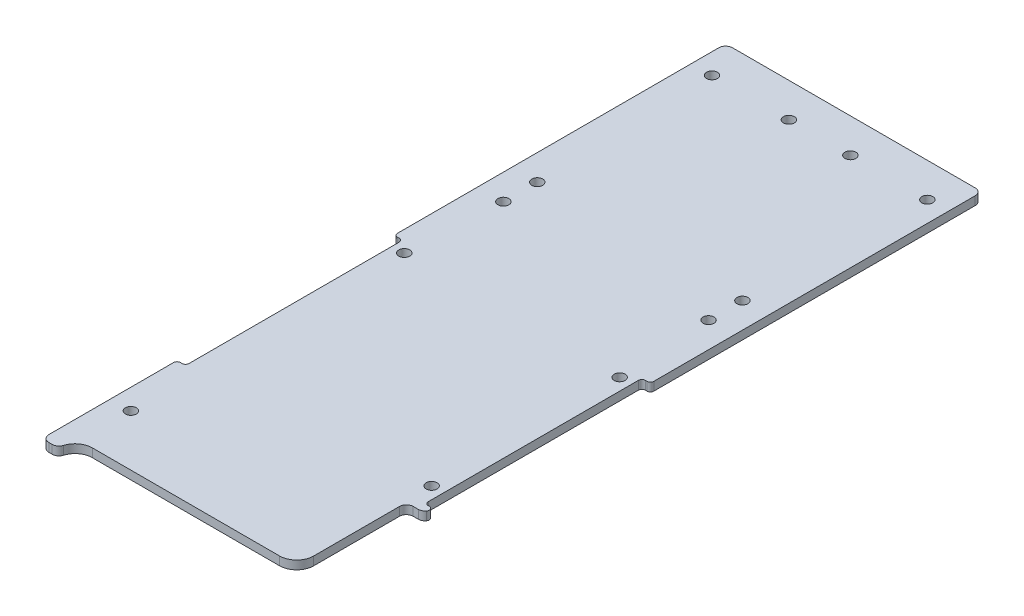
SolidWorks part; units mm, degrees
ref_plane "Front Plane" through (0, 0, 0) normal (0, 0, 1) x (1, 0, 0)
ref_plane "Top Plane" through (0, 0, 0) normal (0, 1, 0) x (1, 0, 0)
ref_plane "Right Plane" through (0, 0, 0) normal (1, 0, 0) x (0, 0, -1)
sketch "Sketch1" plane through (0, 0, 0) normal (0, 1, 0) x (1, 0, 0)
  line L0 (-39.9997, 0) -> (-39.9997, 114.3) construction
  line L1 (-47.625, 127) -> (47.625, 127)
  line L2 (-47.625, 127) -> (-47.625, -127)
  line L3 (-47.625, -127) -> (47.625, -127)
  line L4 (47.625, 127) -> (47.625, -127)
  line L5 (-47.625, 127) -> (47.625, -127) construction
  line L6 (-47.625, -127) -> (47.625, 127) construction
  line L7 (0, 0) -> (0, 127) construction
  line L8 (-39.9997, 0) -> (-39.9997, -101.6) construction
  line L9 (-39.9997, 0) -> (0, 0) construction
  line L10 (-41.275, -127) -> (-41.275, -120.65)
  line L11 (-41.275, -120.65) -> (41.275, -120.65)
  line L12 (41.275, -120.65) -> (41.275, -127)
  line L13 (-39.9997, 114.3) -> (-11.4247, 114.3) construction
  line L14 (39.9997, 114.3) -> (11.4247, 114.3) construction
  circle A0 centre (-39.9997, 114.3) radius 2.032
  circle A1 centre (-39.9997, 0) radius 2.032
  circle A2 centre (-39.9997, -101.6) radius 2.032
  circle A3 centre (39.9997, -101.6) radius 2.032
  circle A4 centre (39.9997, 0) radius 2.032
  circle A5 centre (39.9997, 114.3) radius 2.032
  circle A6 centre (-11.4247, 114.3) radius 2.032
  circle A7 centre (11.4247, 114.3) radius 2.032
  circle A8 centre (-39.9997, -69.85) radius 2.032
  circle A9 centre (39.9997, -69.85) radius 2.032
  point P0 (0, 0)
  dimension "D4" = 4.064
  dimension "D10" = 28.575
  dimension "D1" = 95.25
  dimension "D2" = 254
  dimension "D3" = 7.6253
  dimension "D5" = 12.7
  dimension "D6" = 25.4
  dimension "D7" = 6.35
  dimension "D8" = 6.35
  dimension "D9" = 6.35
  dimension "D11" = 69.85
extrude "Boss-Extrude1" add sketch "Sketch1" along normal blind 3.175 contours L4 L1 L2 L3 A4 A0 A1 A2 A3 A5 | A8 | A3 region at (0, 0, -2.6944) region at (39.9997, 0, 101.6) region at (-39.9997, 0, 69.85)
fillet "Fillet1" radius 2.54 4 edges at (-47.625, 1.5875, -127) (47.625, 1.5875, -127) (47.625, 1.5875, 127) (-47.625, 1.5875, 127)
fillet "Fillet2" radius 2.54 2 edges at (41.275, 1.5875, 127) (-41.275, 1.5875, 127)
fillet "Fillet3" radius 6.35 2 edges at (41.275, 1.5875, 120.65) (-41.275, 1.5875, 120.65)
sketch "Sketch2" plane through (0, 0, 0) normal (0, -1, 0) x (1, 0, 0)
  line L1 (43.815, 127) -> (45.085, 127) construction
  line L2 (40.6451, 123.5787) -> (40.6451, 79.8881)
  line L3 (40.6451, 79.8881) -> (47.625, 79.8881)
  line L11 (47.625, -124.46) -> (47.625, 124.46) construction
  line L12 (43.815, 127) -> (45.085, 127)
  line L13 (47.625, 79.8881) -> (47.625, 124.46)
  arc A0 (35.2956, 120.65) -> (41.3809, 125.1857) centre (35.2956, 127) ccw construction
  arc A1 (43.815, 127) -> (41.3809, 125.1857) centre (43.815, 124.46) ccw construction
  arc A2 (47.625, 124.46) -> (45.085, 127) centre (45.085, 124.46) ccw construction
  arc A3 (40.6451, 123.5787) -> (41.3809, 125.1857) centre (35.2956, 127) ccw
  arc A4 (43.815, 127) -> (41.3809, 125.1857) centre (43.815, 124.46) ccw
  arc A5 (47.625, 124.46) -> (45.085, 127) centre (45.085, 124.46) ccw
  dimension "D2" = 47.1119
  dimension "D1" = 6.9799
extrude "Cut-Extrude1" cut sketch "Sketch2" against normal through all
fillet "Fillet4" radius 6.35 1 edges at (40.6451, 1.5875, 123.5787)
fillet "Fillet5" radius 2.54 2 edges at (47.625, 1.5875, 79.8881) (40.6451, 1.5875, 79.8881)
sketch "Sketch3" plane through (0, 0, 0) normal (0, -1, 0) x (1, 0, 0)
  line L0 (-36.3024, -49.7791) -> (-39.9092, -49.7791) construction
  line L1 (-40.4172, -49.276) -> (-40.4172, -45.7043) construction
  line L2 (-35.7944, -45.7043) -> (-35.7944, -49.276) construction
  line L3 (-39.9092, -45.2013) -> (-36.3024, -45.2013) construction
  line L4 (-36.3024, -37.2027) -> (-39.9092, -37.2027) construction
  line L5 (-35.7944, -33.1279) -> (-35.7944, -36.6996) construction
  line L6 (-40.4172, -36.6996) -> (-40.4172, -33.1279) construction
  line L7 (-39.9092, -32.6249) -> (-36.3024, -32.6249) construction
  line L8 (36.2908, -32.6249) -> (39.8976, -32.6249) construction
  line L9 (40.4056, -33.1279) -> (40.4056, -36.6996) construction
  line L10 (39.8976, -37.2027) -> (36.2908, -37.2027) construction
  line L11 (35.7828, -36.6996) -> (35.7828, -33.1279) construction
  line L12 (36.2908, -45.2013) -> (39.8976, -45.2013) construction
  line L13 (35.7828, -49.276) -> (35.7828, -45.7043) construction
  line L14 (40.4056, -45.7043) -> (40.4056, -49.276) construction
  line L15 (39.8976, -49.7791) -> (36.2908, -49.7791) construction
  line L16 (-36.3024, -49.7791) -> (-39.9092, -49.7791)
  line L17 (-40.4172, -49.276) -> (-40.4172, -45.7043)
  line L18 (-35.7944, -45.7043) -> (-35.7944, -49.276)
  line L19 (-39.9092, -45.2013) -> (-36.3024, -45.2013)
  line L20 (-36.3024, -37.2027) -> (-39.9092, -37.2027)
  line L21 (-35.7944, -33.1279) -> (-35.7944, -36.6996)
  line L22 (-40.4172, -36.6996) -> (-40.4172, -33.1279)
  line L23 (-39.9092, -32.6249) -> (-36.3024, -32.6249)
  line L24 (36.2908, -32.6249) -> (39.8976, -32.6249)
  line L25 (40.4056, -33.1279) -> (40.4056, -36.6996)
  line L26 (39.8976, -37.2027) -> (36.2908, -37.2027)
  line L27 (35.7828, -36.6996) -> (35.7828, -33.1279)
  line L28 (36.2908, -45.2013) -> (39.8976, -45.2013)
  line L29 (35.7828, -49.276) -> (35.7828, -45.7043)
  line L30 (40.4056, -45.7043) -> (40.4056, -49.276)
  line L31 (39.8976, -49.7791) -> (36.2908, -49.7791)
  line L32 (-47.625, -25.836) -> (47.625, -25.836)
  line L33 (-47.625, -124.46) -> (-47.625, 124.46) construction
  line L34 (47.625, -124.46) -> (47.625, 77.3481) construction
  line L35 (0, -25.836) -> (0, -56.0686) construction
  line L1362 (-40.4172, -34.9138) -> (-35.7944, -34.9138)
  line L1857 (-38.1058, -32.6249) -> (-38.1058, -37.2027)
  line L1858 (-38.1058, -45.2013) -> (-38.1058, -49.7791)
  line L1859 (-40.4172, -47.4902) -> (-35.7944, -47.4902)
  circle A0 centre (-38.1058, -34.9138) radius 2.032
  circle A1 centre (-38.1058, -47.4902) radius 2.032
  circle A2 centre (38.1058, -47.4902) radius 2.032
  circle A3 centre (38.1058, -34.9138) radius 2.032
  ellipse E0 centre (-39.9092, -45.7043) end of major axis (-39.4012, -45.7043) minor radius 0.5031 (-39.9092, -45.2013) -> (-40.4172, -45.7043) ccw construction
  ellipse E1 centre (-39.9092, -49.276) end of major axis (-39.4012, -49.276) minor radius 0.5031 (-40.4172, -49.276) -> (-39.9092, -49.7791) ccw construction
  ellipse E6 centre (-36.3024, -49.276) end of major axis (-35.7944, -49.276) minor radius 0.5031 (-36.3024, -49.7791) -> (-35.7944, -49.276) ccw construction
  ellipse E7 centre (-36.3024, -45.7043) end of major axis (-35.7944, -45.7043) minor radius 0.5031 (-35.7944, -45.7043) -> (-36.3024, -45.2013) ccw construction
  ellipse E8 centre (-39.9092, -36.6996) end of major axis (-39.4012, -36.6996) minor radius 0.5031 (-40.4172, -36.6996) -> (-39.9092, -37.2027) ccw construction
  ellipse E9 centre (-36.3024, -36.6996) end of major axis (-35.7944, -36.6996) minor radius 0.5031 (-36.3024, -37.2027) -> (-35.7944, -36.6996) ccw construction
  ellipse E10 centre (-36.3024, -33.1279) end of major axis (-35.7944, -33.1279) minor radius 0.5031 (-35.7944, -33.1279) -> (-36.3024, -32.6249) ccw construction
  ellipse E11 centre (-39.9092, -33.1279) end of major axis (-39.4012, -33.1279) minor radius 0.5031 (-39.9092, -32.6249) -> (-40.4172, -33.1279) ccw construction
  ellipse E12 centre (39.8976, -33.1279) end of major axis (40.4056, -33.1279) minor radius 0.5031 (40.4056, -33.1279) -> (39.8976, -32.6249) ccw construction
  ellipse E13 centre (36.2908, -33.1279) end of major axis (36.7988, -33.1279) minor radius 0.5031 (36.2908, -32.6249) -> (35.7828, -33.1279) ccw construction
  ellipse E14 centre (39.8976, -36.6996) end of major axis (40.4056, -36.6996) minor radius 0.5031 (39.8976, -37.2027) -> (40.4056, -36.6996) ccw construction
  ellipse E15 centre (36.2908, -36.6996) end of major axis (36.7988, -36.6996) minor radius 0.5031 (35.7828, -36.6996) -> (36.2908, -37.2027) ccw construction
  ellipse E16 centre (36.2908, -45.7043) end of major axis (36.7988, -45.7043) minor radius 0.5031 (36.2908, -45.2013) -> (35.7828, -45.7043) ccw construction
  ellipse E17 centre (36.2908, -49.276) end of major axis (36.7988, -49.276) minor radius 0.5031 (35.7828, -49.276) -> (36.2908, -49.7791) ccw construction
  ellipse E18 centre (39.8976, -45.7043) end of major axis (40.4056, -45.7043) minor radius 0.5031 (40.4056, -45.7043) -> (39.8976, -45.2013) ccw construction
  ellipse E19 centre (39.8976, -49.276) end of major axis (40.4056, -49.276) minor radius 0.5031 (39.8976, -49.7791) -> (40.4056, -49.276) ccw construction
  ellipse E20 centre (-39.9092, -45.7043) end of major axis (-39.4012, -45.7043) minor radius 0.5031 (-39.9092, -45.2013) -> (-40.4172, -45.7043) ccw
  ellipse E21 centre (-39.9092, -49.276) end of major axis (-39.4012, -49.276) minor radius 0.5031 (-40.4172, -49.276) -> (-39.9092, -49.7791) ccw
  ellipse E22 centre (-36.3024, -49.276) end of major axis (-35.7944, -49.276) minor radius 0.5031 (-36.3024, -49.7791) -> (-35.7944, -49.276) ccw
  ellipse E23 centre (-36.3024, -45.7043) end of major axis (-35.7944, -45.7043) minor radius 0.5031 (-35.7944, -45.7043) -> (-36.3024, -45.2013) ccw
  ellipse E24 centre (-39.9092, -36.6996) end of major axis (-39.4012, -36.6996) minor radius 0.5031 (-40.4172, -36.6996) -> (-39.9092, -37.2027) ccw
  ellipse E25 centre (-36.3024, -36.6996) end of major axis (-35.7944, -36.6996) minor radius 0.5031 (-36.3024, -37.2027) -> (-35.7944, -36.6996) ccw
  ellipse E26 centre (-36.3024, -33.1279) end of major axis (-35.7944, -33.1279) minor radius 0.5031 (-35.7944, -33.1279) -> (-36.3024, -32.6249) ccw
  ellipse E27 centre (-39.9092, -33.1279) end of major axis (-39.4012, -33.1279) minor radius 0.5031 (-39.9092, -32.6249) -> (-40.4172, -33.1279) ccw
  ellipse E28 centre (39.8976, -33.1279) end of major axis (40.4056, -33.1279) minor radius 0.5031 (40.4056, -33.1279) -> (39.8976, -32.6249) ccw
  ellipse E29 centre (36.2908, -33.1279) end of major axis (36.7988, -33.1279) minor radius 0.5031 (36.2908, -32.6249) -> (35.7828, -33.1279) ccw
  ellipse E30 centre (39.8976, -36.6996) end of major axis (40.4056, -36.6996) minor radius 0.5031 (39.8976, -37.2027) -> (40.4056, -36.6996) ccw
  ellipse E31 centre (36.2908, -36.6996) end of major axis (36.7988, -36.6996) minor radius 0.5031 (35.7828, -36.6996) -> (36.2908, -37.2027) ccw
  ellipse E32 centre (36.2908, -45.7043) end of major axis (36.7988, -45.7043) minor radius 0.5031 (36.2908, -45.2013) -> (35.7828, -45.7043) ccw
  ellipse E33 centre (36.2908, -49.276) end of major axis (36.7988, -49.276) minor radius 0.5031 (35.7828, -49.276) -> (36.2908, -49.7791) ccw
  ellipse E34 centre (39.8976, -45.7043) end of major axis (40.4056, -45.7043) minor radius 0.5031 (40.4056, -45.7043) -> (39.8976, -45.2013) ccw
  ellipse E35 centre (39.8976, -49.276) end of major axis (40.4056, -49.276) minor radius 0.5031 (39.8976, -49.7791) -> (40.4056, -49.276) ccw
  dimension "D2" = 4.064
extrude "Cut-Extrude2" cut sketch "Sketch3" against normal through all contours A0 | A1 | A2 | A3
sketch "Sketch4" plane through (0, 3.175, 0) normal (0, 1, 0) x (1, 0, 0)
  line L11 (-47.625, 124.46) -> (-47.625, -124.46) construction
  line L12 (-47.625, -76.835) -> (-44.45, -76.835)
  line L13 (-47.625, -76.835) -> (-47.625, 3.81)
  line L15 (-47.625, 3.81) -> (-44.45, 3.81)
  line L16 (-44.45, -76.835) -> (-44.45, 3.81)
  line L17 (47.625, 124.46) -> (47.625, -77.3481) construction
  line L18 (47.625, -76.835) -> (44.45, -76.835)
  line L19 (47.625, -76.835) -> (47.625, 3.81)
  line L20 (47.625, 3.81) -> (44.45, 3.81)
  line L45 (44.45, -76.835) -> (44.45, 3.81)
  line L47 (43.1851, -79.8881) -> (45.085, -79.8881) construction
  dimension "D1" = 3.175
  dimension "D2" = 80.645
  dimension "D3" = 3.0531
extrude "Cut-Extrude3" cut sketch "Sketch4" against normal through all and the other way through all
fillet "Fillet6" radius 1.27 8 edges at (-44.45, 1.5875, -3.81) (-47.625, 1.5875, -3.81) (-47.625, 1.5875, 76.835) (-44.45, 1.5875, 76.835) (44.45, 1.5875, 76.835) (47.625, 1.5875, 76.835) (44.45, 1.5875, -3.81) (47.625, 1.5875, -3.81)
